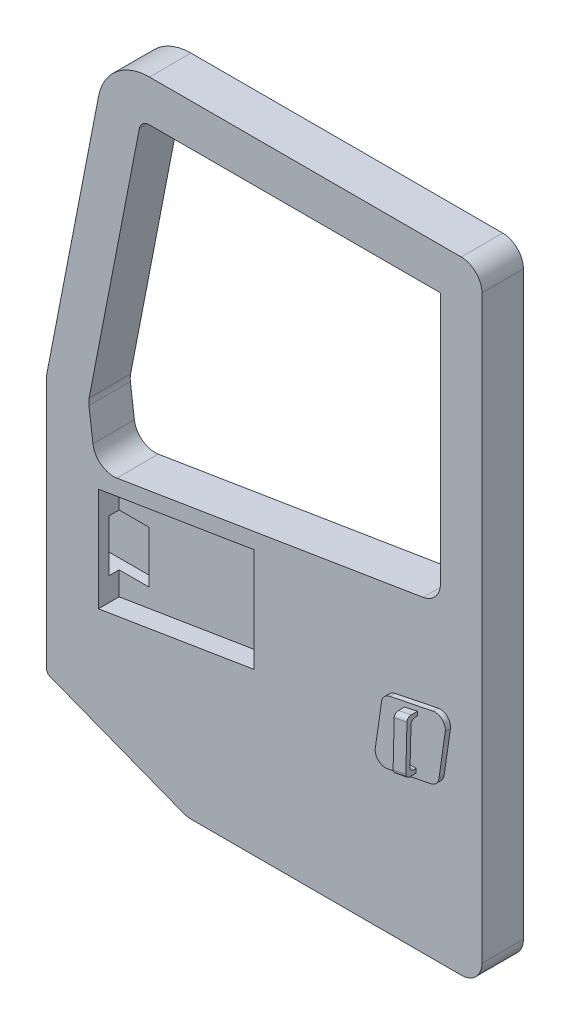
SolidWorks part; units mm, degrees
ref_plane "Front Plane" through (0, 0, 0) normal (0, 0, 1) x (1, 0, 0)
ref_plane "Top Plane" through (0, 0, 0) normal (0, 1, 0) x (1, 0, 0)
ref_plane "Right Plane" through (0, 0, 0) normal (1, 0, 0) x (0, 0, -1)
sketch "Sketch2" plane through (0, 0, 0) normal (0, 0, 1) x (1, 0, 0)
  line L0 (-405.8971, 659.2079) -> (-532.5433, 7.5919)
  line L1 (-179.7693, -762.022) -> (482.6, -762.022)
  line L3 (-281.2299, 761.978) -> (482.6, 761.978)
  line L4 (533.4, -711.222) -> (533.4, 711.178)
  line L5 (-459.8603, -656.939) -> (-452.0517, -645.784) construction
  line L6 (-417.9715, 597.0829) -> (44.1715, -63.1001) construction
  line L8 (-525.2852, -631.9868) -> (-198.1028, -758.5984)
  line L9 (-306.1633, 639.824) -> (-429.1581, 6.9955)
  line L10 (-429.6693, -9.2299) -> (-419.7789, -85.4932)
  line L14 (-281.2299, 660.378) -> (431.8, 660.378)
  line L15 (389.1621, -6.9365) -> (-361.2381, -129.0997)
  line L16 (431.7995, 43.2033) -> (431.8, 660.378)
  line L17 (431.8, -660.422) -> (431.8, 660.378) construction
  line L18 (-170.2829, -660.422) -> (431.8, -660.422) construction
  line L20 (-354.461, -589.1496) -> (-170.2829, -660.422) construction
  line L21 (-55.5325, -79.3316) -> (521.0599, 744.3665) construction
  line L22 (-306.1633, 639.824) -> (-430.7268, -1.0758) construction
  line L23 (-430.7268, -1.0758) -> (-354.461, -589.1496) construction
  line L24 (-416.9351, -673.9156) -> (-198.1028, -758.5984) construction
  line L25 (-179.7693, -762.022) -> (482.6, -762.022)
  line L27 (-281.2299, 761.978) -> (482.6, 761.978)
  line L28 (533.4, -711.222) -> (533.4, 711.178)
  line L29 (-459.8603, -656.939) -> (521.0599, 744.3665) construction
  line L30 (-417.9715, 597.0829) -> (521.0843, -744.3822) construction
  line L31 (-533.4018, 0.6529) -> (-448.7537, -652.0554) construction
  line L34 (-281.2299, 761.978) -> (482.6, 761.978)
  line L35 (-533.4018, 0.6529) -> (-533.4018, -620.1427)
  line L36 (-179.7693, -762.022) -> (482.6, -762.022)
  line L37 (533.4, 711.178) -> (533.4, -711.222)
  line L38 (-417.9715, 597.0829) -> (521.0843, -744.3822) construction
  line L39 (-460.0617, -657.2267) -> (521.0599, 744.3665) construction
  arc A0 (-405.8971, 659.2079) -> (-281.2299, 761.978) centre (-281.2299, 634.978) cw
  arc A2 (-532.5433, 7.5919) -> (-533.4018, 0.6529) centre (-482.6765, -2.1001) ccw
  arc A3 (533.4, 711.178) -> (482.6, 761.978) centre (482.6, 711.178) ccw
  arc A4 (482.6, -762.022) -> (533.4, -711.222) centre (482.6, -711.222) ccw
  arc A5 (-198.1028, -758.5984) -> (-179.7693, -762.022) centre (-179.7693, -711.222) ccw
  arc A7 (-354.461, -589.1496) -> (-354.461, -589.1496) centre (-354.461, -589.1496) ccw
  arc A8 (-170.2829, -660.422) -> (-170.2829, -660.422) centre (-170.2829, -660.422) ccw
  arc A9 (431.8, -660.422) -> (431.8, -660.422) centre (431.8, -660.422) ccw
  arc A10 (431.8, 660.378) -> (431.8, 660.378) centre (431.8, 660.378) ccw
  arc A11 (-306.1633, 639.824) -> (-281.2299, 660.378) centre (-281.2299, 634.978) cw
  arc A12 (-429.1581, 6.9955) -> (-429.6693, -9.2299) centre (-379.2912, -2.6964) ccw
  arc A13 (-430.7268, -1.0758) -> (-430.7268, -1.0758) centre (-430.7268, -1.0758) ccw construction
  arc A14 (431.7995, 43.2033) -> (389.1621, -6.9365) centre (380.9995, 43.2034) cw
  arc A15 (-419.7789, -85.4932) -> (-361.2381, -129.0997) centre (-369.4008, -78.9598) ccw
  arc A16 (-448.7537, -652.0554) -> (-416.9351, -673.9156) centre (-390.71, -601.6569) ccw construction
  arc A17 (-533.4018, -620.1427) -> (-525.2852, -631.9868) centre (-520.7018, -620.1427) ccw
  point P0 (0, 0)
  point P16 (-533.4, -0.0244)
  point P56 (0, 0)
  point P61 (0, 0)
  dimension "D3" = 127
  dimension "D5" = 50.8
  dimension "D6" = 50.8
  dimension "D8" = 50.8
  dimension "D2" = 12.7
  dimension "D1" = 1066.8
  dimension "D4" = 1524
  dimension "D7" = 101.6
extrude "Boss-Extrude1" add sketch "Sketch2" along normal mid plane 101.6 contours L8 A5 L1 A4 L4 A3 L3 A0 L0 A2 A15 L10 A12 L9 A11 L14 L16 A14 L15 region at (29.3865, -188.1823, 0)
sketch "Sketch3" plane through (0, 0, 50.8) normal (0, 0, 1) x (1, 0, 0)
  line L0 (320.1959, -245.101) -> (425.9265, -223.6716)
  line L3 (314.9201, -401.6691) -> (420.6507, -380.2397)
  line L4 (456.113, -252.1835) -> (440.7462, -358.9639)
  line L5 (300.1004, -266.3768) -> (284.7336, -373.1572)
  line L6 (310.4001, -194.8067) -> (287.3499, -354.9772) construction
  line L7 (-487.6326, -408.8312) -> (533.4008, -201.8888) construction
  line L8 (-457.3598, -558.1943) -> (563.6737, -351.2518) construction
  line L9 (461.2461, -216.515) -> (438.1959, -376.6855) construction
  line L10 (373.0612, -234.3863) -> (367.7854, -390.9544) construction
  line L11 (360.2667, -236.9795) -> (354.9908, -393.5476)
  line L12 (385.8558, -231.7931) -> (380.58, -388.3612)
  line L13 (360.3684, -233.9586) -> (355.0926, -390.5267) construction
  line L14 (385.754, -234.814) -> (380.4782, -391.3821) construction
  arc A0 (300.1004, -266.3768) -> (320.1959, -245.101) centre (325.2414, -269.9949) cw
  arc A1 (284.7336, -373.1572) -> (314.9201, -401.6691) centre (309.8746, -376.7752) ccw
  arc A2 (440.7462, -358.9639) -> (420.6507, -380.2397) centre (415.6052, -355.3458) cw
  arc A3 (456.113, -252.1835) -> (425.9265, -223.6716) centre (430.972, -248.5655) ccw
  dimension "D3" = 25.4
  dimension "D1" = 152.4
  dimension "D2" = 152.4
  dimension "D4" = 12.7
  dimension "D5" = 12.7
extrude "Boss-Extrude2" add sketch "Sketch3" along normal blind 12.7 contours L5 A1 L3 L11 L0 A0 | L4 A3 L0 L12 L3 A2 | L12 L0 L11 L3 region at (325.2101, -323.7797, 50.8) region at (370.4233, -312.6704, 50.8) region at (415.6365, -301.561, 50.8)
sketch "Sketch5" plane through (0, 0, 50.8) normal (0, 0, 1) x (1, 0, 0)
  line L0 (-429.6693, -9.2299) -> (-419.7789, -85.4932) construction
  line L1 (389.1621, -6.9365) -> (-361.2381, -129.0997) construction
  line L2 (431.7995, 43.2033) -> (431.8, 660.378) construction
  line L3 (-281.2299, 660.378) -> (431.8, 660.378) construction
  line L4 (-306.1633, 639.824) -> (-429.1581, 6.9955) construction
  line L5 (-429.6693, -9.2299) -> (-419.7789, -85.4932)
  line L6 (-179.7693, -762.022) -> (482.6, -762.022)
  line L12 (-179.7693, -762.022) -> (482.6, -762.022)
  line L18 (389.1621, -6.9365) -> (-361.2381, -129.0997)
  line L19 (431.7995, 43.2033) -> (431.8, 660.378)
  line L20 (-281.2299, 660.378) -> (431.8, 660.378)
  line L21 (-306.1633, 639.824) -> (-429.1581, 6.9955)
  line L28 (387.9598, -243.0291) -> (384.7172, -375.8602)
  line L29 (353.4927, -382.1888) -> (356.7353, -249.3577)
  line L30 (387.9598, -243.0291) -> (356.7353, -249.3577)
  line L31 (384.7172, -375.8602) -> (353.4927, -382.1888)
  line L32 (320.1959, -245.101) -> (425.9265, -223.6716) construction
  line L33 (314.9201, -401.6691) -> (420.6507, -380.2397) construction
  line L34 (320.1959, -245.101) -> (425.9265, -223.6716) construction
  line L35 (314.9201, -401.6691) -> (420.6507, -380.2397) construction
  arc A0 (-419.7789, -85.4932) -> (-361.2381, -129.0997) centre (-369.4008, -78.9598) ccw construction
  arc A1 (389.1621, -6.9365) -> (431.7995, 43.2033) centre (380.9995, 43.2034) ccw construction
  arc A2 (-281.2299, 660.378) -> (-306.1633, 639.824) centre (-281.2299, 634.978) ccw construction
  arc A3 (-429.1581, 6.9955) -> (-429.6693, -9.2299) centre (-379.2912, -2.6964) ccw construction
  arc A4 (-419.7789, -85.4932) -> (-361.2381, -129.0997) centre (-369.4008, -78.9598) ccw
  arc A5 (389.1621, -6.9365) -> (431.7995, 43.2033) centre (380.9995, 43.2034) ccw
  arc A18 (-281.2299, 660.378) -> (-306.1633, 639.824) centre (-281.2299, 634.978) ccw
  arc A19 (-429.1581, 6.9955) -> (-429.6693, -9.2299) centre (-379.2912, -2.6964) ccw
  dimension "D2" = 11.43
  dimension "D3" = 11.43
  dimension "D1" = 0
extrude "Boss-Extrude4" add sketch "Sketch5" along normal blind 38.1 contours L31 L28 L30 L29 region at (370.7262, -312.609, 50.8)
sketch "Sketch6" plane through (393.6581, -9.61, 0) normal (0.9997, -0.0244, 0) x (0, 0, -1)
  line L9 (-63.5, -356.1994) -> (-78.74, -356.1994)
  line L10 (-78.74, -356.1994) -> (-78.74, -243.6487)
  line L11 (-78.74, -243.6487) -> (-63.5, -243.6487)
  line L12 (-63.5, -356.1994) -> (-78.74, -356.1994)
  line L13 (-78.74, -356.1994) -> (-78.74, -243.6487)
  line L14 (-78.74, -243.6487) -> (-63.5, -243.6487)
  line M5 (-63.5, -366.3594) -> (-63.5, -233.4887)
  dimension "D1" = 10.16
extrude "Cut-Extrude6" cut sketch "Sketch6" against normal through all and the other way through all contours L14 L13 L12 M5 region at (386.3385, -309.4447, 71.12)
fillet "Fillet5" radius 10.16 4 edges at (369.1049, -379.0245, 88.9) (369.4394, -365.3242, 78.74) (372.1861, -252.8071, 78.74) (372.3476, -246.1934, 88.9)
sketch "Sketch7" plane through (-533.4018, 59.3738, 0) normal (1, 0, 0) x (0, 0, 1)
  line L0 (0, 821.3958) -> (0, -702.6042) construction
  line L1 (50.8, 821.3958) -> (-50.8, 821.3958) construction
  line L2 (50.8, -702.6042) -> (-50.8, -702.6042) construction
  line L3 (50.8, 58.7209) -> (-50.8, 58.7209) construction
  line L4 (-31.75, 84.1209) -> (31.75, 84.1209)
  line L5 (-31.75, 84.1209) -> (-31.75, 236.5209)
  line L6 (-31.75, 236.5209) -> (31.75, 236.5209)
  line L11 (31.75, 84.1209) -> (31.75, 236.5209)
  line L12 (-31.75, 84.1209) -> (31.75, 236.5209) construction
  line L13 (-31.75, 236.5209) -> (31.75, 84.1209) construction
  line L21 (-31.75, 642.9209) -> (31.75, 642.9209)
  line L28 (-31.75, 642.9209) -> (-31.75, 490.5209)
  line L29 (-31.75, 490.5209) -> (31.75, 490.5209)
  line L30 (31.75, 642.9209) -> (31.75, 490.5209)
  line L31 (-31.75, 642.9209) -> (31.75, 490.5209) construction
  line L32 (-31.75, 490.5209) -> (31.75, 642.9209) construction
  point P6 (0, 160.3209)
  point P13 (0, 566.7209)
  dimension "D1" = 63.5
  dimension "D2" = 152.4
  dimension "D3" = 25.4
  dimension "D4" = 254
extrude "Boss-Extrude5" add sketch "Sketch7" against normal blind 12.7
sketch "Sketch13" plane through (-546.1018, 0, 0) normal (-1, 0, 0) x (0, 0, 1)
  line L0 (0, -24.7471) -> (0, -177.1471) construction
  line L3 (-31.75, -24.7471) -> (31.75, -24.7471) construction
  line L6 (31.75, -177.1471) -> (-31.75, -177.1471) construction
  line L9 (31.75, -100.9471) -> (-31.75, -100.9471) construction
  line L10 (31.75, -24.7471) -> (31.75, -177.1471) construction
  line L11 (-31.75, -177.1471) -> (-31.75, -24.7471) construction
  line L12 (0, -431.1471) -> (0, -583.5471) construction
  line L13 (-31.75, -431.1471) -> (31.75, -431.1471) construction
  line L14 (31.75, -583.5471) -> (-31.75, -583.5471) construction
  line L15 (31.75, -507.3471) -> (-31.75, -507.3471) construction
  line L16 (31.75, -431.1471) -> (31.75, -583.5471) construction
  line L17 (-31.75, -583.5471) -> (-31.75, -431.1471) construction
  circle A4 centre (0, -50.1471) radius 11.43
  circle A6 centre (0, -151.7471) radius 11.43
  circle A7 centre (0, -456.5471) radius 11.43
  circle A8 centre (0, -558.1471) radius 11.43
  dimension "D1" = 50.8
  dimension "D2" = 22.86
  dimension "D3" = 50.8
  dimension "D4" = 22.86
extrude "Cut-Extrude7" cut sketch "Sketch13" against normal blind 46.99
sketch "Sketch14" plane through (-533.4018, 0, 0) normal (-1, 0, 0) x (0, 0, 1)
  line L0 (0, 761.978) -> (0, -758.5984) construction
  line L3 (50.8, 761.978) -> (-50.8, 761.978) construction
  line L4 (50.8, -758.5984) -> (-50.8, -758.5984) construction
  line L6 (-25.4, -371.7817) -> (25.4, -371.7817)
  line L7 (-25.4, -371.7817) -> (-25.4, -244.7817)
  line L8 (-25.4, -244.7817) -> (25.4, -244.7817)
  line L9 (25.4, -371.7817) -> (25.4, -244.7817)
  line L10 (-25.4, -371.7817) -> (25.4, -244.7817) construction
  line L11 (-25.4, -244.7817) -> (25.4, -371.7817) construction
  point P6 (0, -308.2817)
  dimension "D2" = 127
sketch "Sketch16" plane through (0, 0, 0) normal (0, 0, 1) x (1, 0, 0)
  line L0 (-406.4018, -175.0538) -> (-25.4018, -113.028)
  line L1 (-406.4018, -175.0538) -> (-406.4018, -429.0538)
  line L2 (-406.4018, -429.0538) -> (-25.4018, -367.028)
  line L3 (-25.4018, -367.028) -> (-25.4018, -113.028)
  line L4 (389.1621, -6.9365) -> (-361.2381, -129.0997) construction
  line L5 (-533.4018, 0.6529) -> (-533.4018, -620.1427) construction
  dimension "D1" = 381
  dimension "D2" = 254
  dimension "D3" = 38.1
  dimension "D4" = 127
extrude "Cut-Extrude8" cut sketch "Sketch16" along normal blind 379.73
extrude "Cut-Extrude9" cut sketch "Sketch14" against normal blind 200.406 contours L7 L8 L9 L6
equation "\"doorwidth\"= 42in"
equation "\"D1@Sketch2\"=\"doorwidth\""
equation "\"doorheight\"= 60in"
equation "\"D4@Sketch2\"=\"doorheight\""
equation "\"doorthickness\"= 4in"
equation "\"D1@Boss-Extrude1\"=\"doorthickness\""
equation "\"hingewidth\"= 2.5in"
equation "\"hingeheight\"= 6in"
equation "\"distanceofhinges\"= 10in"
equation "\"actuator slot width\"= 2in"
equation "\"actuator slot height\"= 5in"
equation "\"D2@Sketch14\"=\"actuator slot height\""
equation "\"D1@Sketch14\"=\"actuator slot width\""
equation "\"D1@Sketch7\"=\"hingewidth\""
equation "\"D2@Sketch7\"=\"hingeheight\""
equation "\"D4@Sketch7\"=\"distanceofhinges\""
